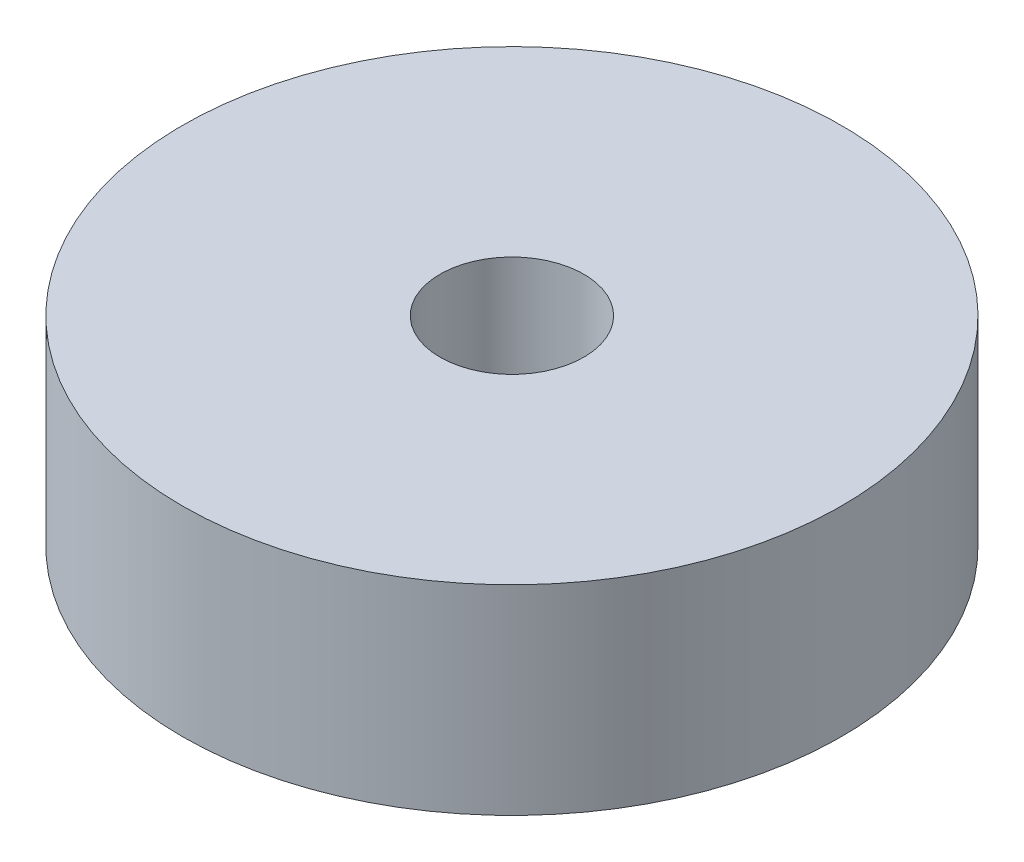
SolidWorks part; units mm, degrees
ref_plane "Front Plane" through (0, 0, 0) normal (0, 0, 1) x (1, 0, 0)
ref_plane "Top Plane" through (0, 0, 0) normal (0, 1, 0) x (1, 0, 0)
ref_plane "Right Plane" through (0, 0, 0) normal (1, 0, 0) x (0, 0, -1)
sketch "Sketch1" plane through (0, 0, 0) normal (0, 1, 0) x (1, 0, 0)
  circle A0 centre (0, 0) radius 10.475
  circle A1 centre (0, 0) radius 7.62
  circle A2 centre (0, 0) radius 2.286
  dimension "D1" = 20.95
  dimension "D2" = 4.572
  dimension "D3" = 15.24
extrude "Boss-Extrude1" add sketch "Sketch1" along normal blind 6.35 contours A0 A1 region at (-10.1787, 0, 0)
extrude "Boss-Extrude2" add sketch "Sketch1<3>" along normal blind 6.35 contours A1 A2 region at (-7.4045, 0, 0)
sketch "Sketch1<3>" plane through (0, 0, 0) normal (0, 1, 0) x (1, 0, 0) same geometry as "Sketch1"
